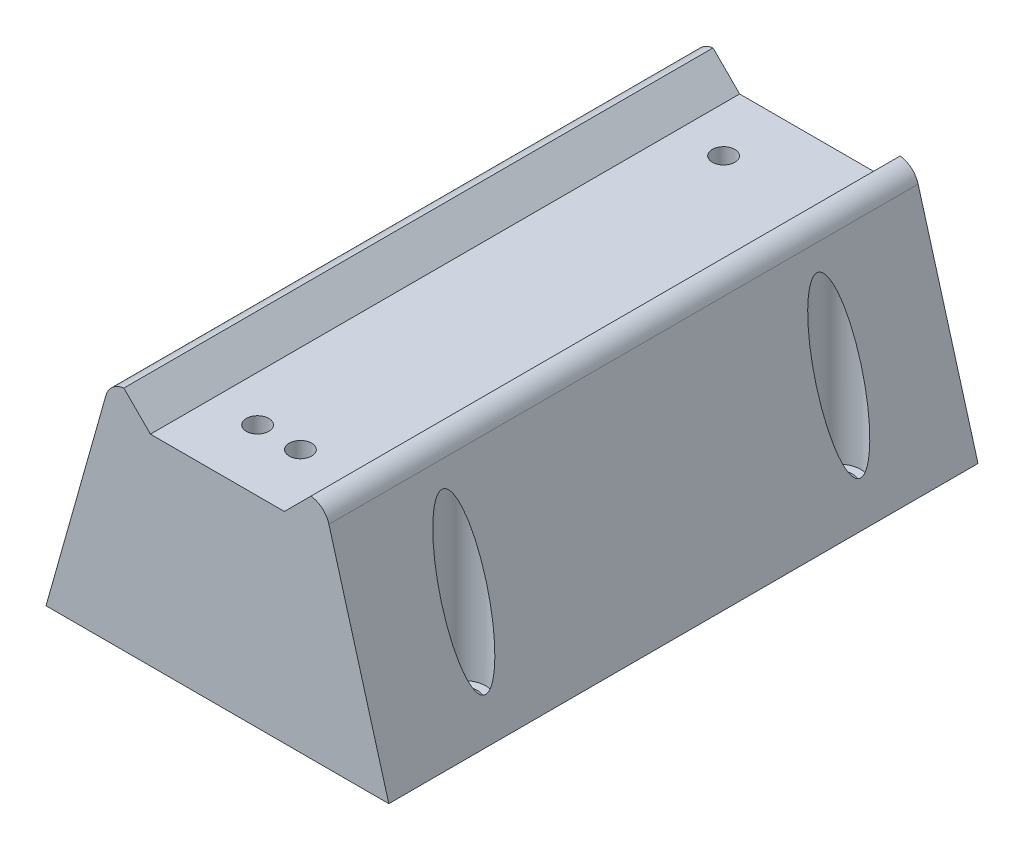
SolidWorks part; units mm, degrees
ref_plane "Front Plane" through (0, 0, 0) normal (0, 0, 1) x (1, 0, 0)
ref_plane "Top Plane" through (0, 0, 0) normal (0, 1, 0) x (1, 0, 0)
ref_plane "Right Plane" through (0, 0, 0) normal (1, 0, 0) x (0, 0, -1)
sketch "Sketch2" plane through (0, 0, 0) normal (0, 0, 1) x (1, 0, 0)
  line L0 (10, -2.5) -> (10, -18.75)
  line L1 (-10, -2.5) -> (10, -2.5)
  line L2 (-10, -2.5) -> (-10, 2.5) construction
  line L3 (-10, 2.5) -> (10, 2.5)
  line L4 (10, -2.5) -> (10, 2.5) construction
  line L5 (-10, -2.5) -> (10, 2.5) construction
  line L6 (-10, 2.5) -> (10, -2.5) construction
  line L7 (10, -18.75) -> (16, -18.75)
  line L8 (16, -18.75) -> (10, 2.5)
  line L9 (0, 0) -> (0, -7.3093) construction
  line L10 (-10, -18.75) -> (-16, -18.75)
  line L11 (-16, -18.75) -> (-10, 2.5)
  line L12 (-10, -2.5) -> (-10, -18.75)
  point P0 (0, 0)
  dimension "D1" = 5
  dimension "D2" = 20
  dimension "D3" = 6
  dimension "D4" = 16.25
extrude "Boss-Extrude1" add sketch "Sketch2" along normal mid plane 50
sketch "Sketch3" plane through (0, 0, 25) normal (0, 0, 1) x (1, 0, 0)
  line L0 (-10, -18.75) -> (10, -18.75)
  line L8 (16, -18.75) -> (10, 2.5)
  line L9 (10, 2.5) -> (-10, 2.5)
  line L10 (-10, 2.5) -> (-16, -18.75)
  line L11 (-16, -18.75) -> (-10, -18.75)
  line L12 (-10, -18.75) -> (-10, -2.5)
  line L13 (-10, -2.5) -> (10, -2.5)
  line L14 (10, -2.5) -> (10, -18.75)
  line L15 (10, -18.75) -> (16, -18.75)
  line L16 (16, -18.75) -> (10, 2.5)
  line L17 (10, 2.5) -> (-10, 2.5)
  line L18 (-10, 2.5) -> (-16, -18.75)
  line L19 (-16, -18.75) -> (-10, -18.75)
  line L23 (10, -18.75) -> (16, -18.75)
  dimension "D1" = 0
extrude "Boss-Extrude2" add sketch "Sketch3" along normal blind 2.5
mirror "Mirror1" about plane through (0, 0, 0) normal (0, 0, 1) of "Boss-Extrude2"
sketch "Sketch4" plane through (0, -2.5, 0) normal (0, -1, 0) x (1, 0, 0)
  line L0 (-3.27, -23.02) -> (-3.27, -20.48) construction
  line L1 (-3.27, -20.48) -> (-0.73, -20.48) construction
  line L2 (-0.73, -20.48) -> (-0.73, -23.02) construction
  line L3 (-0.73, -23.02) -> (-3.27, -23.02) construction
  line L4 (0.73, 23.02) -> (3.27, 23.02) construction
  line L5 (3.27, 23.02) -> (3.27, 20.48) construction
  line L6 (3.27, 20.48) -> (0.73, 20.48) construction
  line L7 (0.73, 20.48) -> (0.73, 23.02) construction
  line L8 (-3.27, 20.48) -> (-3.27, 23.02) construction
  line L9 (-3.27, 23.02) -> (-0.73, 23.02) construction
  line L10 (-0.73, 23.02) -> (-0.73, 20.48) construction
  line L11 (-0.73, 20.48) -> (-3.27, 20.48) construction
  line L12 (-3.27, -23.02) -> (-3.27, -20.48)
  line L13 (-3.27, -20.48) -> (-0.73, -20.48)
  line L14 (-0.73, -20.48) -> (-0.73, -23.02)
  line L15 (-0.73, -23.02) -> (-3.27, -23.02)
  line L16 (0.73, 23.02) -> (3.27, 23.02)
  line L17 (3.27, 23.02) -> (3.27, 20.48)
  line L18 (3.27, 20.48) -> (0.73, 20.48)
  line L19 (0.73, 20.48) -> (0.73, 23.02)
  line L20 (-3.27, 20.48) -> (-3.27, 23.02)
  line L21 (-3.27, 23.02) -> (-0.73, 23.02)
  line L22 (-0.73, 23.02) -> (-0.73, 20.48)
  line L23 (-0.73, 20.48) -> (-3.27, 20.48)
  circle A0 centre (-2, -21.75) radius 0.6985 construction
  circle A1 centre (2, 21.75) radius 0.6985 construction
  circle A2 centre (-2, 21.75) radius 0.6985 construction
  circle A3 centre (-2, -21.75) radius 0.6985
  circle A4 centre (2, 21.75) radius 0.6985
  circle A5 centre (-2, 21.75) radius 0.6985
sketch "Sketch5" plane through (0, -2.5, 0) normal (0, -1, 0) x (1, 0, 0)
  line L84 (-0.23, 23.52) -> (-3.77, 23.52)
  line L85 (-3.77, 23.52) -> (-3.77, 19.98)
  line L86 (-3.77, 19.98) -> (-0.23, 19.98)
  line L87 (-0.23, 19.98) -> (-0.23, 23.52)
  line L88 (-3.27, 23.02) -> (-3.27, 20.48)
  line L89 (-0.73, 23.02) -> (-3.27, 23.02)
  line L90 (-0.73, 20.48) -> (-0.73, 23.02)
  line L91 (-3.27, 20.48) -> (-0.73, 20.48)
  line L92 (-3.27, 23.02) -> (-3.27, 20.48)
  line L93 (-0.73, 23.02) -> (-3.27, 23.02)
  line L94 (-0.73, 20.48) -> (-0.73, 23.02)
  line L95 (-3.27, 20.48) -> (-0.73, 20.48)
  line L96 (3.27, 23.02) -> (0.73, 23.02)
  line L97 (3.27, 20.48) -> (3.27, 23.02)
  line L98 (0.73, 20.48) -> (3.27, 20.48)
  line L99 (0.73, 23.02) -> (0.73, 20.48)
  line L100 (3.27, 23.02) -> (0.73, 23.02)
  line L101 (3.27, 20.48) -> (3.27, 23.02)
  line L102 (0.73, 20.48) -> (3.27, 20.48)
  line L103 (0.73, 23.02) -> (0.73, 20.48)
  line L104 (-3.27, -20.48) -> (-3.27, -23.02)
  line L105 (-0.73, -20.48) -> (-3.27, -20.48)
  line L106 (-0.73, -23.02) -> (-0.73, -20.48)
  line L107 (-3.27, -23.02) -> (-0.73, -23.02)
  line L108 (-3.27, -20.48) -> (-3.27, -23.02)
  line L109 (-0.73, -20.48) -> (-3.27, -20.48)
  line L110 (-0.73, -23.02) -> (-0.73, -20.48)
  line L111 (-3.27, -23.02) -> (-0.73, -23.02)
  line L112 (3.77, 23.52) -> (0.23, 23.52)
  line L113 (0.23, 23.52) -> (0.23, 19.98)
  line L114 (0.23, 19.98) -> (3.77, 19.98)
  line L115 (3.77, 19.98) -> (3.77, 23.52)
  line L116 (-0.23, -19.98) -> (-3.77, -19.98)
  line L117 (-3.77, -19.98) -> (-3.77, -23.52)
  line L118 (-3.77, -23.52) -> (-0.23, -23.52)
  line L119 (-0.23, -23.52) -> (-0.23, -19.98)
  line L120 (10, 25) -> (10, -25) construction
  line L121 (-10, 25) -> (10, 25)
  line L122 (-10, 25) -> (-10, 17.5)
  line L123 (-10, 17.5) -> (10, 17.5)
  line L124 (10, 25) -> (10, 17.5)
  line L125 (10, 25) -> (10, -25) construction
  line L126 (-10, -25) -> (10, -25)
  line L127 (-10, -25) -> (-10, -17.5)
  line L128 (-10, -17.5) -> (10, -17.5)
  line L129 (10, -25) -> (10, -17.5)
  line L130 (-0.23, 19.98) -> (0.23, 19.98)
  line L131 (-0.23, 23.52) -> (0.23, 23.52)
  circle A1 centre (-2, 21.75) radius 0.6985
  circle A2 centre (-2, 21.75) radius 0.6985
  circle A3 centre (2, 21.75) radius 0.6985
  circle A4 centre (2, 21.75) radius 0.6985
  circle A5 centre (-2, -21.75) radius 0.6985
  circle A6 centre (-2, -21.75) radius 0.6985
  line M17 (-10, -25) -> (10, -25)
  line M18 (10, -25) -> (10, 25)
  line M19 (10, 25) -> (-10, 25)
  line M20 (-10, 25) -> (-10, -25)
  dimension "D8" = 7.5
  dimension "D9" = 7.5
  dimension "D1" = 0
  dimension "D2" = 0
  dimension "D3" = 0
  dimension "D4" = 0
  dimension "D5" = 0
  dimension "D6" = 0
  dimension "D7" = 0.5
extrude "Boss-Extrude3" add sketch "Sketch5" along normal blind 10 contours L123 L87 L86 L85 L84 L115 L114 L113 L112 M20 M18 M19 | L128 L119 L118 L117 L116 M20 M17 M18 region at (0, -2.5, 24.7864) region at (0.1823, -2.5, -21.2044)
sketch "Sketch6" plane through (0, 2.5, 0) normal (0, 1, 0) x (1, 0, 0)
  circle A0 centre (2, -21.75) radius 0.6985 construction
  circle A1 centre (-2, -21.75) radius 0.6985 construction
  circle A2 centre (-2, 21.75) radius 0.6985 construction
  circle A3 centre (2, -21.75) radius 0.6985 construction
  circle A4 centre (-2, -21.75) radius 0.6985 construction
  circle A5 centre (-2, 21.75) radius 0.6985 construction
  circle A6 centre (-2, 21.75) radius 1.0485
  circle A7 centre (-2, -21.75) radius 1.0485
  circle A8 centre (2, -21.75) radius 1.0485
  dimension "D1" = 0.35
extrude "Cut-Extrude1" cut sketch "Sketch6" against normal through all
fillet "Fillet1" radius 2 6 edges at (10, 2.5, 0) (-10, 2.5, 0) (0, -12.5, 17.5) (0, -12.5, -17.5) (-10, -2.5, 0) (10, -2.5, 0)
sketch "Sketch7" plane through (0, -18.75, 0) normal (0, -1, 0) x (1, 0, 0)
  line L0 (-16, 27.5) -> (-16, -27.5) construction
  line L1 (-16, 27.5) -> (16, 27.5) construction
  line L2 (0, -55) -> (0, 55) construction
  line L3 (55, 0) -> (-55, 0) construction
  circle A0 centre (-13, 17.5) radius 1.25
  circle A1 centre (13, 17.5) radius 1.25
  circle A2 centre (13, -17.5) radius 1.25
  circle A3 centre (-13, -17.5) radius 1.25
  point P0 (-13, 17.5)
  point P8 (13, 17.5)
  point P12 (13, -17.5)
  point P14 (-13, -17.5)
  dimension "D3" = 2.5
  dimension "D1" = 3
  dimension "D2" = 10
hole_wizard "M2 Clearance Hole1" positions "Sketch7" profile "Sketch8" hole size "M2" standard "ANSI Metric" end condition through all
sketch "Sketch8" plane through (-13, -18.75, 17.5) normal (1, 0, 0) x (0, 0, -1)
  line L0 (0, 0) -> (0, 21.25)
  line L1 (0, 21.25) -> (1.3, 21.25)
  line L2 (1.3, 21.25) -> (1.3, 0)
  line L5 (1.3, 0) -> (0, 0)
  line L11 (0, -6.35) -> (0, 107.95) construction
  dimension "Thru Hole Dia." = 2.6
  dimension "Thru Hole Depth" = 21.25
ref_plane "Plane1" through (0, -16.75, 0) normal (0, -1, 0) x (-1, 0, 0)
sketch "Sketch9" plane through (0, -16.75, 0) normal (0, -1, 0) x (1, 0, 0)
  circle A0 centre (-13, -17.5) radius 1.3 construction
  circle A1 centre (13, -17.5) radius 1.3 construction
  circle A2 centre (13, 17.5) radius 1.3 construction
  circle A3 centre (-13, 17.5) radius 1.3 construction
  circle A4 centre (-13, -17.5) radius 1.3 construction
  circle A5 centre (13, -17.5) radius 1.3 construction
  circle A6 centre (13, 17.5) radius 1.3 construction
  circle A7 centre (-13, 17.5) radius 1.3 construction
  circle A8 centre (-13, -17.5) radius 2.05
  circle A9 centre (13, -17.5) radius 2.05
  circle A10 centre (13, 17.5) radius 2.05
  circle A11 centre (-13, 17.5) radius 2.05
  dimension "D1" = 0.75
extrude "Cut-Extrude4" cut sketch "Sketch9" against normal through all
sketch "Sketch10" plane through (0, 2.5, 0) normal (0, 1, 0) x (1, 0, 0)
  line L0 (8.4865, 27.5) -> (-8.4865, 27.5) construction
  line L1 (-6.25, -27.5) -> (6.25, -27.5)
  line L2 (-6.25, -27.5) -> (-6.25, 27.5)
  line L3 (-6.25, 27.5) -> (6.25, 27.5)
  line L4 (6.25, -27.5) -> (6.25, 27.5)
  line L5 (-6.25, -27.5) -> (6.25, 27.5) construction
  line L6 (-6.25, 27.5) -> (6.25, -27.5) construction
  point P0 (0, 0)
  dimension "D1" = 12.5
extrude "Cut-Extrude5" cut sketch "Sketch10" against normal blind 2.5
chamfer "Chamfer1" distance 2.5 angle 45 2 edges at (6.25, 2.5, 0) (-6.25, 2.5, 0)
